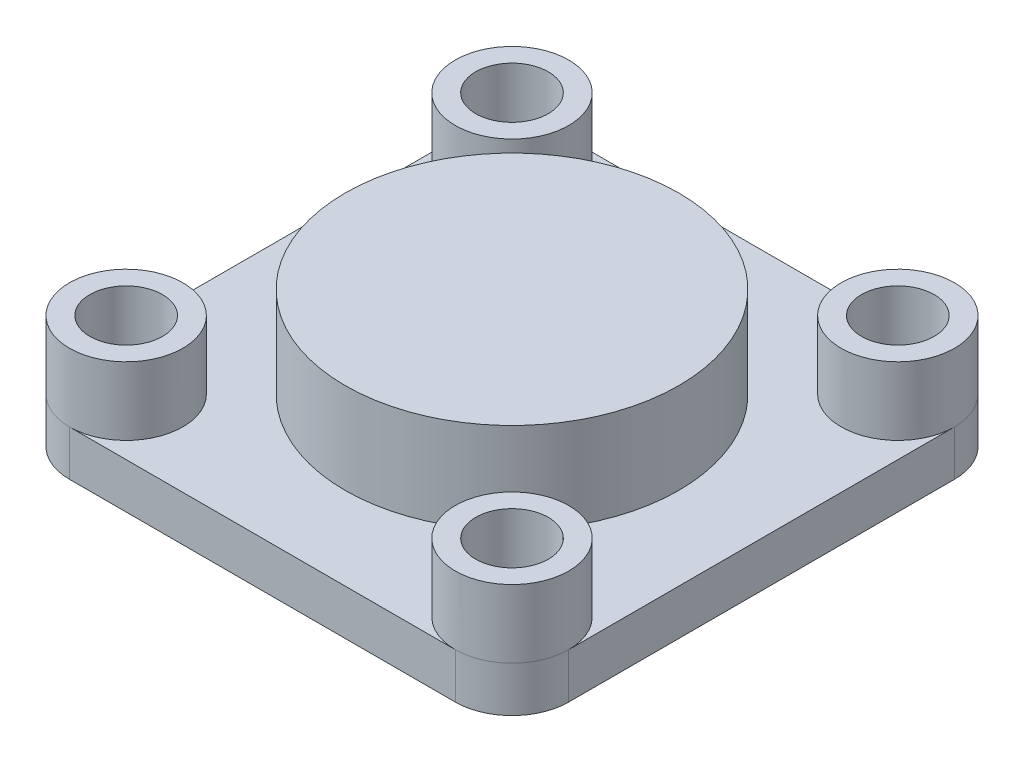
SolidWorks part; units mm, degrees
ref_plane "Спереди" through (0, 0, 0) normal (0, 0, 1) x (1, 0, 0)
ref_plane "Сверху" through (0, 0, 0) normal (0, 1, 0) x (1, 0, 0)
ref_plane "Справа" through (0, 0, 0) normal (1, 0, 0) x (0, 0, -1)
other "Configuration Table"
sketch "Sketch1" plane through (0, 0, 0) normal (0, 1, 0) x (1, 0, 0)
  line L1 (-11, 11) -> (11, 11)
  line L2 (-11, 11) -> (-11, -11)
  line L3 (-11, -11) -> (11, -11)
  line L4 (11, 11) -> (11, -11)
  dimension "D1" = 22
  dimension "D2" = 22
  dimension "D3" = 11
  dimension "D4" = 11
extrude "Boss-Extrude1" add sketch "Sketch1" along normal blind 2
sketch "Sketch2" plane through (0, 2, 0) normal (0, 1, 0) x (1, 0, 0)
  circle A0 centre (0, 0) radius 7.35
  dimension "D1" = 14.7
extrude "Boss-Extrude2" add sketch "Sketch2" along normal blind 4
sketch "Sketch3" plane through (0, 2, 0) normal (0, 1, 0) x (1, 0, 0)
  circle A0 centre (-8.5, -8.5) radius 2.5
  dimension "D1" = 5
  dimension "D2" = 8.5
  dimension "D3" = 8.5
extrude "Boss-Extrude3" add sketch "Sketch3" along normal blind 3
sketch "Sketch4" plane through (0, 5, 0) normal (0, 1, 0) x (1, 0, 0)
  circle A0 centre (-8.5, -8.5) radius 1.6
  circle A2 centre (-8.5, -8.5) radius 2.5 construction
  dimension "D1" = 3.2
extrude "Cut-Extrude1" cut sketch "Sketch4" against normal through all
ref_axis "Axis1" through (0, 6, 0) along (0, -1, 0)
pattern_circular "CirPattern1" count 4 every 90 about axis through (0, 6, 0) along (0, -1, 0) of "Boss-Extrude3", "Cut-Extrude1"
fillet "Fillet1" radius 2.5 4 edges at (11, 1, -11) (-11, 1, -11) (11, 1, 11) (-11, 1, 11)
